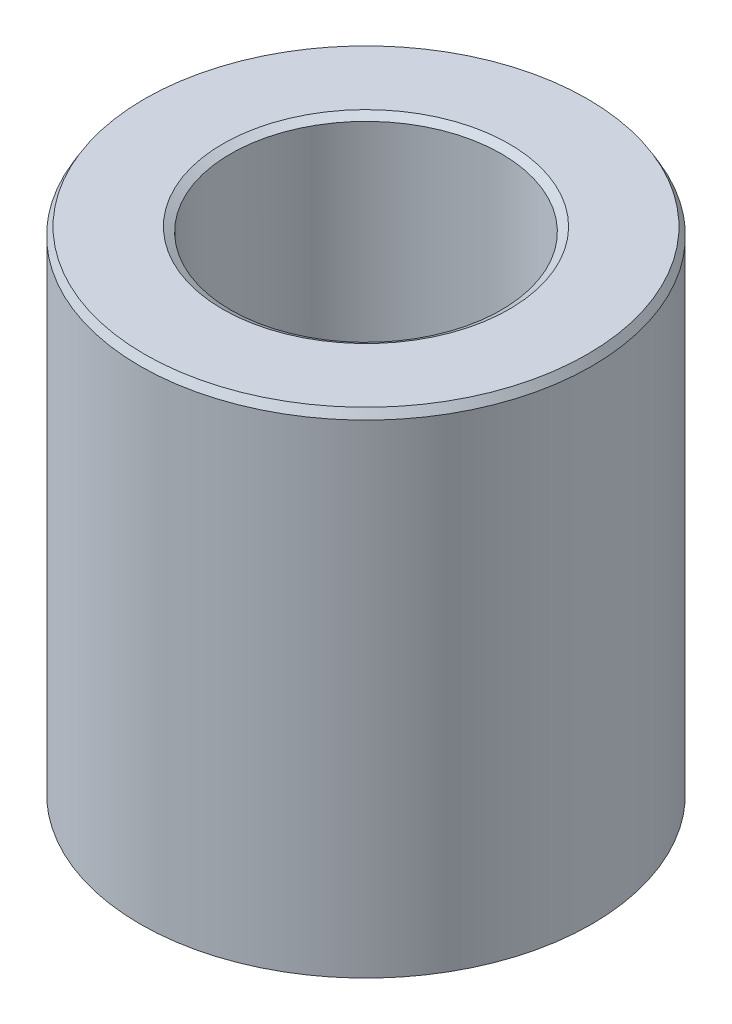
SolidWorks part; units mm, degrees
ref_plane "Front Plane" through (0, 0, 0) normal (0, 0, 1) x (1, 0, 0)
ref_plane "Top Plane" through (0, 0, 0) normal (0, 1, 0) x (1, 0, 0)
ref_plane "Right Plane" through (0, 0, 0) normal (1, 0, 0) x (0, 0, -1)
sketch "Sketch1" plane through (0, 0, 0) normal (0, 1, 0) x (1, 0, 0)
  circle A0 centre (0, 0) radius 55
  dimension "SLEEVE_OD" = 110
extrude "Boss-Extrude1" add sketch "Sketch1" along normal blind 120.6948
sketch "Sketch2" plane through (0, 0, 0) normal (0, 1, 0) x (1, 0, 0)
  circle A0 centre (0, 0) radius 32.9556
  dimension "BORE_D" = 65.9111
extrude "Cut-Extrude1" cut sketch "Sketch2" along normal through all
chamfer "Chamfer1" distance 1.9283 angle 30 4 edges at (0, 120.6948, 32.9556) (0, 0, 32.9556) (0, 0, 55) (0, 120.6948, 55) first distance on face at (0, 120.6948, 32.9556) first distance on face at (0, 0, 32.9556) first distance on face at (0, 120.6948, 55)
